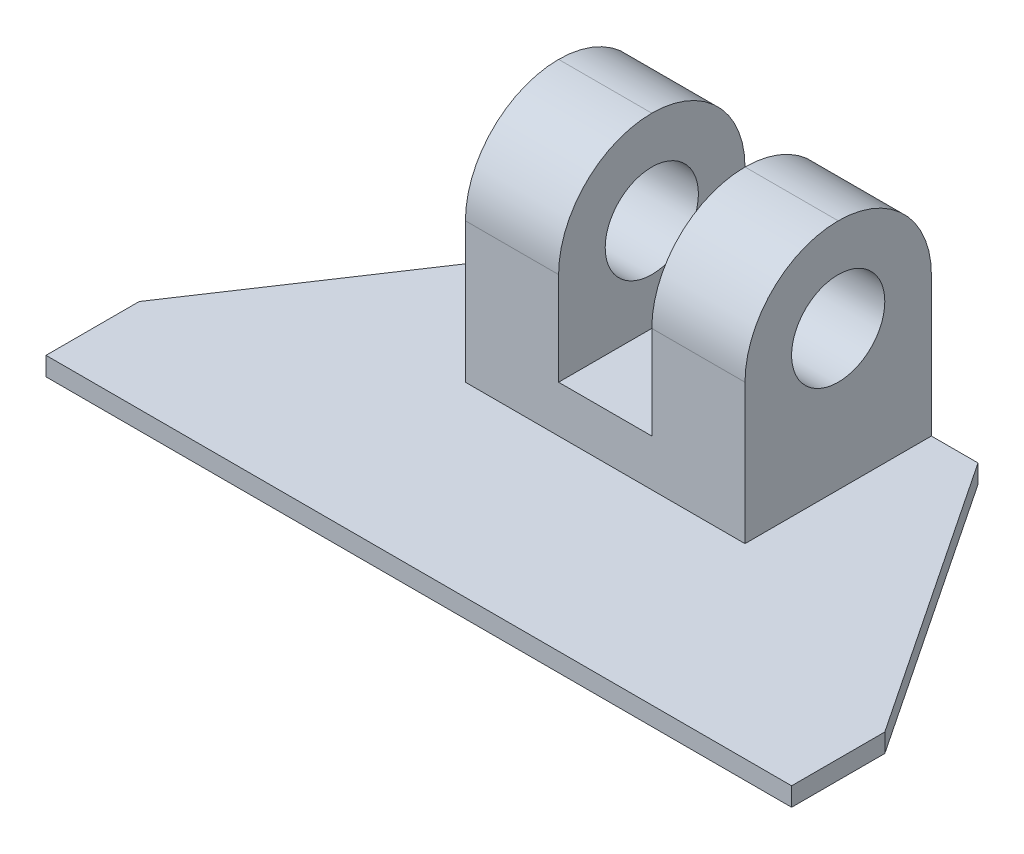
SolidWorks part; units mm, degrees
ref_plane "Front Plane" through (0, 0, 0) normal (0, 0, 1) x (1, 0, 0)
ref_plane "Top Plane" through (0, 0, 0) normal (0, 1, 0) x (1, 0, 0)
ref_plane "Right Plane" through (0, 0, 0) normal (1, 0, 0) x (0, 0, -1)
sketch "Sketch1" plane through (0, 0, 0) normal (0, 1, 0) x (1, 0, 0)
  line L1 (0, 0) -> (-80, 0)
  line L2 (0, 0) -> (0, 40)
  line L3 (0, 40) -> (-80, 40)
  line L4 (-80, 0) -> (-80, 40)
  dimension "D1" = 40
  dimension "D2" = 80
extrude "Boss-Extrude1" add sketch "Sketch1" along normal blind 2
sketch "Sketch2" plane through (0, 2, 0) normal (0, 1, 0) x (1, 0, 0)
  line L0 (-80, 10) -> (-60, 40)
  line L1 (-80, 40) -> (-80, 0) construction
  line L2 (0, 40) -> (-80, 40) construction
  line L3 (-60, 40) -> (-80, 40)
  line L4 (-80, 40) -> (-80, 10)
  line L5 (0, 10) -> (-20, 40)
  line L6 (0, 0) -> (0, 40) construction
  line L7 (-20, 40) -> (0, 40)
  line L8 (0, 40) -> (0, 10)
  line L9 (-80, 0) -> (0, 0) construction
  point P12 (-80, 9.7345)
  point P17 (-80, 10)
  point P18 (-80, 10)
  point P19 (0, 10)
  point P20 (-21.1798, 40)
  point P21 (0, 0)
  dimension "D1" = 10
  dimension "D2" = 40
extrude "Cut-Extrude1" cut sketch "Sketch2" against normal blind 5
sketch "Sketch3" plane through (0, 2, 0) normal (0, 1, 0) x (1, 0, 0)
  line L0 (-20, 40) -> (-60, 40) construction
  line L1 (-55, 40) -> (-25, 40)
  line L2 (-55, 40) -> (-55, 20)
  line L3 (-55, 20) -> (-25, 20)
  line L4 (-25, 40) -> (-25, 20)
  line L5 (-80, 10) -> (-80, 0) construction
  dimension "D1" = 30
  dimension "D2" = 25
  dimension "D3" = 20
extrude "Boss-Extrude2" add sketch "Sketch3" along normal blind 25
sketch "Sketch4" plane through (-25, 0, 0) normal (1, 0, 0) x (0, 0, -1)
  line L0 (20, 27) -> (20, 2) construction
  line L1 (20, 27) -> (40, 27) construction
  circle A0 centre (30, 17) radius 5
  point P6 (12.4185, 28.0247)
  dimension "D1" = 10
  dimension "D2" = 10
  dimension "D3" = 10
extrude "Cut-Extrude2" cut sketch "Sketch4" against normal through all
sketch "Sketch5" plane through (0, 27, 0) normal (0, 1, 0) x (1, 0, 0)
  line L0 (-55, 20) -> (-25, 20) construction
  line L1 (-45, 20) -> (-35, 20)
  line L2 (-45, 20) -> (-45, 40)
  line L3 (-45, 40) -> (-35, 40)
  line L4 (-35, 20) -> (-35, 40)
  line L5 (-25, 20) -> (-25, 40) construction
  dimension "D1" = 10
  dimension "D2" = 10
  dimension "D3" = 20
extrude "Cut-Extrude3" cut sketch "Sketch5" against normal blind 20
fillet "Fillet1" radius 10 4 edges at (-30, 27, -20) (-50, 27, -20) (-50, 27, -40) (-30, 27, -40)
